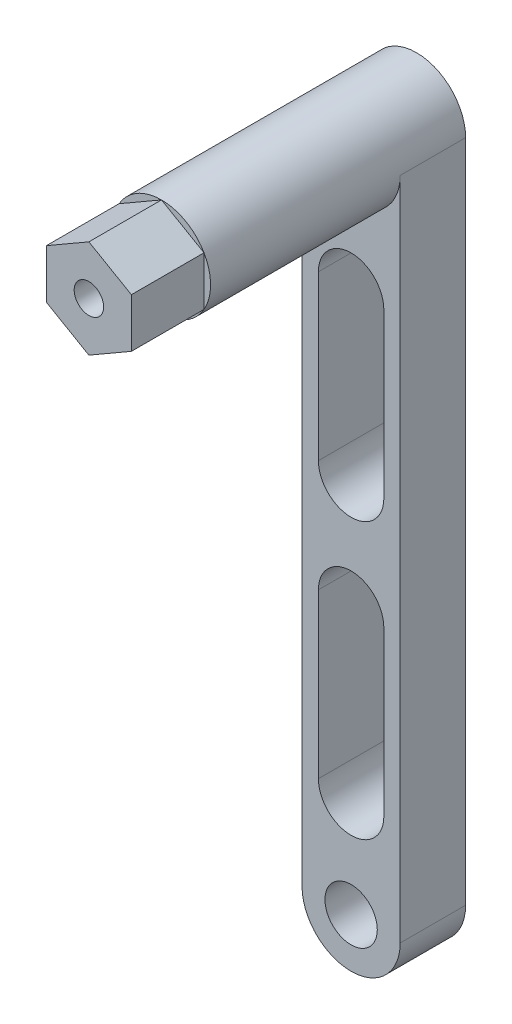
SolidWorks part; units mm, degrees
material "PEI"
ref_plane "Front Plane" through (0, 0, 0) normal (0, 0, 1) x (1, 0, 0)
ref_plane "Top Plane" through (0, 0, 0) normal (0, 1, 0) x (1, 0, 0)
ref_plane "Right Plane" through (0, 0, 0) normal (1, 0, 0) x (0, 0, -1)
sketch "Sketch1" plane through (0, 0, 0) normal (0, 0, 1) x (1, 0, 0)
  line L0 (0, -50.8) -> (0, 50.8) construction
  line L1 (-7.5, -50.8) -> (-7.5, 50.8)
  line L2 (7.5, -50.8) -> (7.5, 50.8)
  line L3 (0, -35.3) -> (0, -10.3) construction
  line L4 (-5, -35.3) -> (-5, -10.3)
  line L5 (5, -35.3) -> (5, -10.3)
  line L6 (0, 31.8) -> (0, 6.8) construction
  line L7 (5, 31.8) -> (5, 6.8)
  line L8 (-5, 31.8) -> (-5, 6.8)
  line L9 (-5, 19.3) -> (5, 19.3) construction
  line L10 (-5, -22.8) -> (5, -22.8) construction
  line L12 (0, 58.3) -> (0, 36.8) construction
  arc A0 (-7.5, -50.8) -> (7.5, -50.8) centre (0, -50.8) ccw
  arc A1 (7.5, 50.8) -> (-7.5, 50.8) centre (0, 50.8) ccw
  circle A2 centre (0, -50.8) radius 4
  arc A4 (-5, -35.3) -> (5, -35.3) centre (0, -35.3) ccw
  arc A5 (5, -10.3) -> (-5, -10.3) centre (0, -10.3) ccw
  arc A6 (5, 31.8) -> (-5, 31.8) centre (0, 31.8) ccw
  arc A7 (-5, 6.8) -> (5, 6.8) centre (0, 6.8) ccw
  circle A8 centre (0, 50.8) radius 7.5
  point P2 (0, 0)
  point P14 (0, -22.8)
  point P19 (0, 19.3)
  point P30 (0, -5.3)
  point P32 (0, -46.8)
  point P33 (0, -40.3)
  point P35 (0, 1.8)
  point P37 (0, 43.3)
  dimension "D3" = 8
  dimension "D1" = 101.6
  dimension "D2" = 15
  dimension "D4" = 10
  dimension "D5" = 6.5
  dimension "20" = 25
  dimension "D6" = 6.5
extrude "Boss-Extrude1" add sketch "Sketch1" along normal blind 10 contours A8 L1 A0 L2 A7 L8 A6 L7 A5 L5 A4 L4 A2 region at (-6.3987, 0, 0)
extrude "Boss-Extrude2" add sketch "Sketch1<4>" along normal blind 38.98 contours A1 A8 region at (0, 50.8, 0)
sketch "Sketch1<4>" plane through (0, 0, 0) normal (0, 0, 1) x (1, 0, 0) same geometry as "Sketch1"
sketch "Sketch2" plane through (0, 0, 38.98) normal (0, 0, 1) x (1, 0, 0)
  point P0 (0, 50.8)
sketch "Sketch3" plane through (0, 0, 38.98) normal (0, 0, 1) x (1, 0, 0)
  line L1 (0, 43.3) -> (6.4952, 47.05)
  line L2 (6.4952, 47.05) -> (6.4952, 54.55)
  line L3 (6.4952, 54.55) -> (0, 58.3)
  line L4 (0, 58.3) -> (-6.4952, 54.55)
  line L5 (-6.4952, 54.55) -> (-6.4952, 47.05)
  line L6 (-6.4952, 47.05) -> (0, 43.3)
  circle A0 centre (0, 50.8) radius 6.4952 construction
extrude "Boss-Extrude3" add sketch "Sketch3" along normal blind 11.1
sketch "Sketch4" plane through (0, 0, 50.08) normal (0, 0, 1) x (1, 0, 0)
  circle A0 centre (0, 50.8) radius 2.25
  dimension "D1" = 4.5
extrude "Cut-Extrude1" cut sketch "Sketch4" against normal blind 10 contours A0
